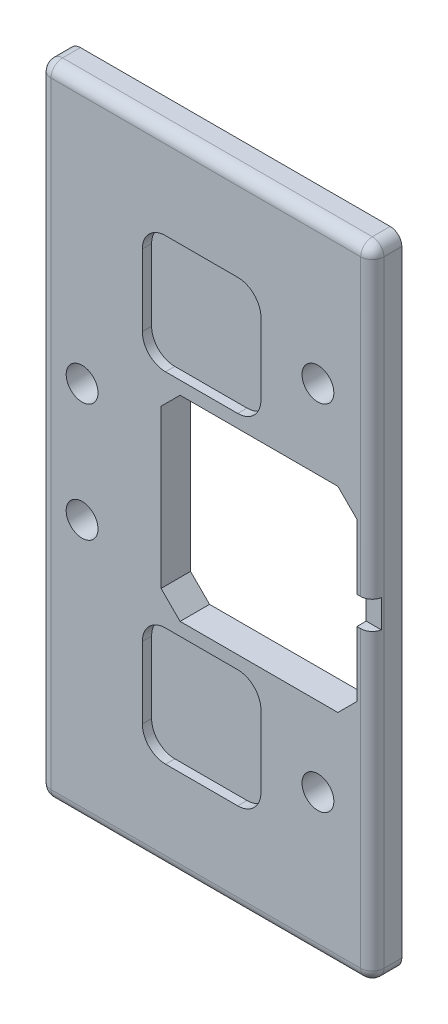
SolidWorks part; units mm, degrees
ref_plane "Front Plane" through (0, 0, 0) normal (0, 0, 1) x (1, 0, 0)
ref_plane "Top Plane" through (0, 0, 0) normal (0, 1, 0) x (1, 0, 0)
ref_plane "Right Plane" through (0, 0, 0) normal (1, 0, 0) x (0, 0, -1)
sketch "Sketch1" plane through (0, 0, 0) normal (0, 0, 1) x (1, 0, 0)
  line L0 (68.0566, 68.87) -> (126.0194, 68.87)
  line L22 (62.2146, 68.87) -> (68.0566, 68.87)
  line L28 (62.2146, -68.87) -> (126.0194, -68.87)
  line L31 (126.0194, -68.87) -> (126.0194, 68.87)
  line L38 (62.2146, 68.87) -> (54.2999, 68.87)
  line L40 (62.2146, -68.87) -> (54.2999, -68.87)
  line L41 (54.2999, 68.87) -> (54.2999, -68.87)
  point P0 (0, 0)
extrude "Boss-Extrude3" add sketch "Sketch1" along normal blind 6.35 contours L22 region at (90.1597, 0, 0)
ref_plane "Plane1" through (0, 0, 0) normal (0, -1, 0) x (-1, 0, 0)
sketch "Sketch6" plane through (0, 0, 0) normal (0, 0, -1) x (-1, 0, 0)
  circle A16 centre (-63.5, 12.7) radius 3.429
  circle A17 centre (-114.3, 38.1) radius 3.429
  circle A18 centre (-114.3, -38.1) radius 3.429
  circle A19 centre (-63.5, -12.7) radius 3.429
  dimension "D1" = 6.858
extrude "Cut-Extrude5" cut sketch "Sketch6" against normal up to surface (6.35 mm away) up to face at (90.1597, 0, 6.35)
fillet "Fillet2" radius 2.5 8 edges at (54.2999, 68.87, 3.175) (54.2999, -68.87, 3.175) (126.0194, -68.87, 3.175) (126.0194, 68.87, 3.175) (90.1597, 68.87, 6.35) (90.1597, -68.87, 6.35) (54.2999, 0, 6.35) (126.0194, 0, 6.35)
sketch "Sketch7" plane through (0, 0, 6.35) normal (0, 0, 1) x (1, 0, 0)
  line L0 (90.1597, -66.37) -> (90.1597, 66.37) construction
  line L3 (56.7999, -66.37) -> (123.5194, -66.37) construction
  line L5 (123.5194, 66.37) -> (56.7999, 66.37) construction
  line L6 (56.7999, 0) -> (123.5194, 0) construction
  line L7 (56.7999, 66.37) -> (56.7999, -66.37) construction
  line L8 (123.5194, -66.37) -> (123.5194, 66.37) construction
  circle A0 centre (90.1597, 0) radius 3.43
  dimension "D1" = 6.86
extrude "Cut-Extrude6" cut sketch "Sketch7" against normal through all
sketch "Sketch10" plane through (0, 0, 6.35) normal (0, 0, 1) x (1, 0, 0)
  line L0 (80.5121, 0) -> (56.7999, 0) construction
  line L14 (80.5121, 21.0947) -> (122.7015, 21.0947)
  line L15 (80.5121, 21.0947) -> (80.5121, -21.0947)
  line L16 (80.5121, -21.0947) -> (122.7015, -21.0947)
  line L17 (122.7015, 21.0947) -> (122.7015, -21.0947)
  line L18 (56.7999, 66.37) -> (56.7999, -66.37) construction
  dimension "D1" = 23.7122
extrude "Cut-Extrude8" cut sketch "Sketch10" against normal through all
sketch "Sketch11" plane through (0, 0, 6.35) normal (0, 0, 1) x (1, 0, 0)
  line L0 (123.5194, -66.37) -> (123.5194, 66.37) construction
  line L1 (123.5194, -3) -> (122.7015, -3)
  line L3 (123.5194, 3) -> (122.7015, 3)
  line L4 (122.7015, -3) -> (122.7015, 3)
  line L5 (122.7015, -21.0947) -> (122.7015, 21.0947) construction
  line L6 (123.1104, 3) -> (123.1104, 66.37) construction
  line L7 (123.5194, -3) -> (127.3985, -3)
  line L9 (123.5194, 3) -> (127.3985, 3)
  line L10 (127.3985, -3) -> (127.3985, 3)
  line L11 (123.5194, 66.37) -> (56.7999, 66.37) construction
  line L12 (123.1104, -3) -> (123.1104, -66.37) construction
  line L13 (56.7999, -66.37) -> (123.5194, -66.37) construction
  dimension "D1" = 6
extrude "Cut-Extrude9" cut sketch "Sketch11" against normal blind 2
sketch "Sketch12" plane through (0, 0, 6.35) normal (0, 0, 1) x (1, 0, 0)
  line L0 (76.4742, -44.3) -> (76.4742, -50.9707) construction
  line L1 (81.4742, -49.3) -> (76.4742, -49.3) construction
  line L2 (96.8742, -23.9) -> (102.0243, -23.9) construction
  line L3 (102.0243, -23.9) -> (101.8742, -28.9) construction
  line L5 (76.4742, -49.3) -> (102.0243, -49.3)
  line L6 (76.4742, -49.3) -> (76.4742, -23.9)
  line L7 (76.4742, -23.9) -> (102.0243, -23.9)
  line L8 (102.0243, -49.3) -> (102.0243, -23.9)
extrude "Cut-Extrude10" cut sketch "Sketch12" against normal blind 2
fillet "Fillet3" radius 5 4 edges at (102.0243, -23.9, 5.35) (76.4742, -23.9, 5.35) (76.4742, -49.3, 5.35) (102.0243, -49.3, 5.35)
mirror "Mirror1" about plane through (0, 0, 0) normal (0, -1, 0) of "Fillet3", "Cut-Extrude10"
chamfer "Chamfer1" distance 4.1 angle 45 4 edges at (80.5121, -21.0947, 3.175) (80.5121, 21.0947, 3.175) (122.7015, 21.0947, 3.175) (122.7015, -21.0947, 3.175)
